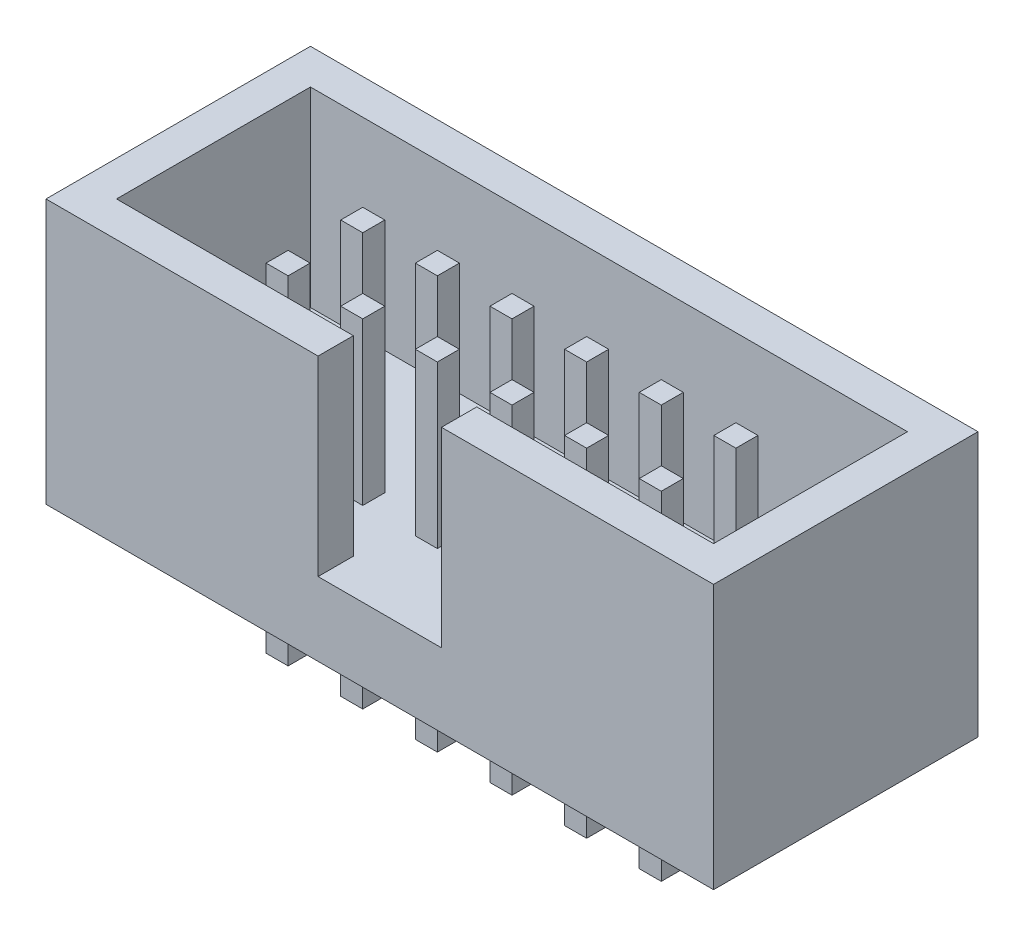
SolidWorks part; units mm, degrees
ref_plane "前视基准面" through (0, 0, 0) normal (0, 0, 1) x (1, 0, 0)
ref_plane "上视基准面" through (0, 0, 0) normal (0, 1, 0) x (1, 0, 0)
ref_plane "右视基准面" through (0, 0, 0) normal (1, 0, 0) x (0, 0, -1)
sketch "草图1" plane through (0, 0, 0) normal (0, 1, 0) x (1, 0, 0)
  line L0 (0, 85.0964) -> (0, -118.2031) construction
  line L1 (-11.36, 4.5) -> (11.36, 4.5)
  line L2 (-11.36, 4.5) -> (-11.36, -4.5)
  line L3 (-11.36, -4.5) -> (11.36, -4.5)
  line L4 (11.36, 4.5) -> (11.36, -4.5)
  line L5 (-200.5452, 0) -> (261.2352, 0) construction
  dimension "D1" = 9
  dimension "D2" = 22.72
extrude "拉伸1" add sketch "草图1" along normal blind 9
sketch "草图2" plane through (0, 9, 0) normal (0, 1, 0) x (-1, 0, 0)
  line L8 (-10.16, 3.3) -> (-10.16, -3.3)
  line L9 (10.16, 3.3) -> (-10.16, 3.3)
  line L10 (10.16, -3.3) -> (10.16, 3.3)
  line L11 (-10.16, -3.3) -> (10.16, -3.3)
  line L12 (-10.16, 3.3) -> (-10.16, -3.3)
  line L13 (10.16, 3.3) -> (-10.16, 3.3)
  line L14 (10.16, -3.3) -> (10.16, 3.3)
  line L15 (-10.16, -3.3) -> (10.16, -3.3)
  dimension "D1" = 1.2
extrude "切除-拉伸1" cut sketch "草图2" against normal blind 6.5
sketch "草图3" plane through (0, 0, 4.5) normal (0, 0, 1) x (1, 0, 0)
  line L0 (-11.36, 9) -> (11.36, 9) construction
  line L1 (-2.1, 9) -> (2.1, 9)
  line L2 (-2.1, 9) -> (-2.1, 2.5)
  line L3 (-2.1, 2.5) -> (2.1, 2.5)
  line L4 (2.1, 9) -> (2.1, 2.5)
  line L5 (-10.16, 2.5) -> (10.16, 2.5) construction
  line L6 (0, 9.4226) -> (0, -4.0288) construction
  dimension "D1" = 4.2
extrude "切除-拉伸2" cut sketch "草图3" against normal blind 6.5
sketch "草图5" plane through (0, 0, 0) normal (0, -1, 0) x (1, 0, 0)
  line L0 (0, 6.0683) -> (0, -6.9786) construction
  line L1 (-14.7999, 0) -> (15.2382, 0) construction
  line L2 (-1.27, 2.5244) -> (-1.27, -0.4442) construction
  line L3 (-1.645, 0.895) -> (-0.895, 0.895)
  line L4 (-1.645, 0.895) -> (-1.645, 1.645)
  line L5 (-1.645, 1.645) -> (-0.895, 1.645)
  line L6 (-0.895, 0.895) -> (-0.895, 1.645)
  line L7 (-2.3518, 1.27) -> (0.5396, 1.27) construction
  line L8 (-4.185, 0.895) -> (-3.435, 0.895)
  line L9 (-4.185, 0.895) -> (-4.185, 1.645)
  line L10 (-4.185, 1.645) -> (-3.435, 1.645)
  line L11 (-3.435, 0.895) -> (-3.435, 1.645)
  line L12 (-6.725, 0.895) -> (-5.975, 0.895)
  line L13 (-6.725, 0.895) -> (-6.725, 1.645)
  line L14 (-6.725, 1.645) -> (-5.975, 1.645)
  line L15 (-5.975, 0.895) -> (-5.975, 1.645)
  line L24 (-5.975, -0.895) -> (-5.975, -1.645)
  line L25 (-6.725, -1.645) -> (-5.975, -1.645)
  line L26 (-6.725, -0.895) -> (-6.725, -1.645)
  line L27 (-6.725, -0.895) -> (-5.975, -0.895)
  line L28 (-3.435, -0.895) -> (-3.435, -1.645)
  line L29 (-4.185, -1.645) -> (-3.435, -1.645)
  line L30 (-4.185, -0.895) -> (-4.185, -1.645)
  line L31 (-4.185, -0.895) -> (-3.435, -0.895)
  line L32 (-0.895, -0.895) -> (-0.895, -1.645)
  line L33 (-1.645, -1.645) -> (-0.895, -1.645)
  line L34 (-1.645, -0.895) -> (-1.645, -1.645)
  line L35 (-1.645, -0.895) -> (-0.895, -0.895)
  line L36 (1.27, 2.5244) -> (1.27, -0.4442) construction
  line L37 (1.645, -0.895) -> (0.895, -0.895)
  line L38 (1.645, -0.895) -> (1.645, -1.645)
  line L39 (1.645, -1.645) -> (0.895, -1.645)
  line L40 (0.895, -0.895) -> (0.895, -1.645)
  line L41 (4.185, -0.895) -> (3.435, -0.895)
  line L42 (4.185, -0.895) -> (4.185, -1.645)
  line L43 (4.185, -1.645) -> (3.435, -1.645)
  line L44 (3.435, -0.895) -> (3.435, -1.645)
  line L45 (6.725, -0.895) -> (5.975, -0.895)
  line L46 (6.725, -0.895) -> (6.725, -1.645)
  line L47 (6.725, -1.645) -> (5.975, -1.645)
  line L48 (5.975, -0.895) -> (5.975, -1.645)
  line L57 (5.975, 0.895) -> (5.975, 1.645)
  line L58 (6.725, 1.645) -> (5.975, 1.645)
  line L59 (6.725, 0.895) -> (6.725, 1.645)
  line L60 (6.725, 0.895) -> (5.975, 0.895)
  line L61 (3.435, 0.895) -> (3.435, 1.645)
  line L62 (4.185, 1.645) -> (3.435, 1.645)
  line L63 (4.185, 0.895) -> (4.185, 1.645)
  line L64 (4.185, 0.895) -> (3.435, 0.895)
  line L65 (0.895, 0.895) -> (0.895, 1.645)
  line L66 (1.645, 1.645) -> (0.895, 1.645)
  line L67 (1.645, 0.895) -> (1.645, 1.645)
  line L68 (1.645, 0.895) -> (0.895, 0.895)
  dimension "D1" = 0.75
  dimension "D2" = 0.75
  dimension "D3" = 1.27
  dimension "D4" = 1.27
extrude "拉伸2" add sketch "草图5" along normal blind 3.5 and the other way offset from surface 1 other way up to face at (0, 9, 1.3)
sketch "草图6" plane through (0, 0, 0) normal (0, -1, 0) x (1, 0, 0)
  line L0 (14.8773, 0) -> (-15.139, 0) construction
  line L1 (0, 6.7624) -> (0, -6.108) construction
  line L3 (-5.975, 1.645) -> (-6.725, 1.645) construction
  line L4 (-6.725, 1.645) -> (-6.725, 0.895) construction
  line L5 (-6.725, 0.895) -> (-5.975, 0.895) construction
  circle A0 centre (-6.35, 1.27) radius 0.375
